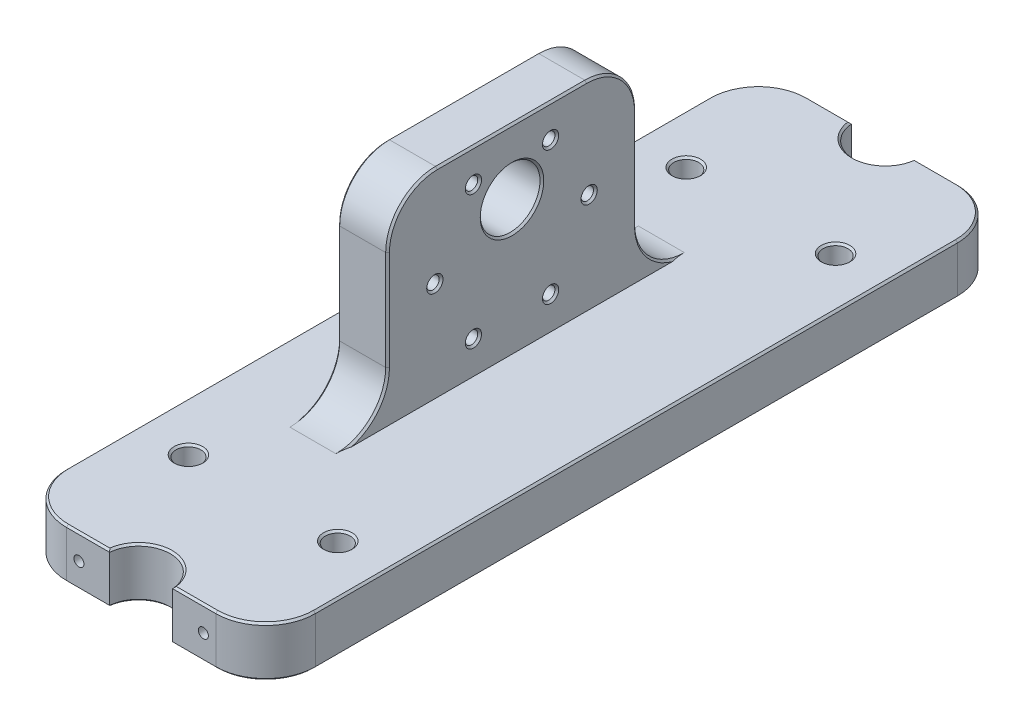
SolidWorks part; units mm, degrees
material "Nylon 101"
ref_plane "Front" through (0, 0, 0) normal (0, 0, 1) x (1, 0, 0)
ref_plane "Top" through (0, 0, 0) normal (0, 1, 0) x (1, 0, 0)
ref_plane "Right" through (0, 0, 0) normal (1, 0, 0) x (0, 0, -1)
sketch "Sketch1" plane through (0, 0, 0) normal (0, 1, 0) x (1, 0, 0)
  line L0 (-25, -75) -> (25, -75) construction
  line L1 (-15, 50) -> (15, 50) construction
  line L2 (0, -75) -> (0, 75) construction
  line L3 (-25, -75) -> (-25, 75)
  line L4 (25, -75) -> (25, 75)
  line L5 (25, 0) -> (0, 0) construction
  line L6 (25, 17) -> (97.2, 17)
  line L7 (25, 17) -> (25, -17)
  line L8 (25, -17) -> (97.2, -17)
  line L9 (97.2, 17) -> (97.2, -17)
  line L10 (-15, 50) -> (-15, -50) construction
  line L11 (-15, -50) -> (15, -50) construction
  line L12 (15, 50) -> (15, -50) construction
  line L13 (-25, -75.5) -> (25, -75.5)
  line L14 (-25, -74.5) -> (25, -74.5)
  line L15 (-25, 75.5) -> (25, 75.5)
  line L16 (-25, 74.5) -> (25, 74.5)
  circle A0 centre (0, 75) radius 6.35
  circle A1 centre (0, -75) radius 6.35
  arc A2 (-25, -75) -> (25, -75) centre (0, -75) ccw
  arc A3 (25, 75) -> (-25, 75) centre (0, 75) ccw
  circle A6 centre (-15, 50) radius 2.5
  circle A7 centre (-15, -50) radius 2.5
  circle A8 centre (15, -50) radius 2.5
  circle A9 centre (15, 50) radius 2.5
  point P8 (0, 0)
  point P24 (0, -50)
  dimension "D2" = 12.7
  dimension "D5" = 25
  dimension "D1" = 5
  dimension "D3" = 150
  dimension "D4" = 25
  dimension "D6" = 25
  dimension "D7" = 34
  dimension "D8" = 72.2
  dimension "D9" = 30
  dimension "D10" = 0.5
  dimension "D11" = 0.5
extrude "Boss-Extrude1" add sketch "Sketch1" along normal blind 10 contours A1 L14 L4 L16 A0 L3 A9 A8 A7 A6 region at (0, 0, 0)
sketch "Sketch2" plane through (0, 0, 0) normal (0, 1, 0) x (1, 0, 0)
  line L1 (0, 25) -> (-10, 25)
  line L2 (0, 25) -> (0, -25)
  line L3 (0, -25) -> (-10, -25)
  line L4 (-10, 25) -> (-10, -25)
  line L6 (25, 0) -> (0, 0) construction
  line L7 (25, 0) -> (0, 0) construction
  dimension "D1" = 50
  dimension "D2" = 10
extrude "Boss-Extrude2" add sketch "Sketch2" along normal blind 50
sketch "Sketch3" plane through (25, 0, 0) normal (1, 0, 0) x (0, 0, -1)
  line L0 (-25, 10) -> (25, 10) construction
  line L1 (0, 10) -> (0, 50) construction
  line L3 (-25, 50) -> (25, 50) construction
  circle A0 centre (0, 30) radius 15.5 construction
  circle A1 centre (0, 30) radius 18.4 construction
  circle A2 centre (-15.5, 30) radius 1.25
  circle A8 centre (0, 37) radius 3 construction
  circle A9 centre (0, 37) radius 6
  circle A10 centre (-7.75, 43.4234) radius 1.25
  circle A11 centre (7.75, 43.4234) radius 1.25
  circle A12 centre (15.5, 30) radius 1.25
  circle A13 centre (7.75, 16.5766) radius 1.25
  circle A14 centre (-7.75, 16.5766) radius 1.25
  dimension "D1" = 31
  dimension "D2" = 2.5
  dimension "D3" = 36.8
  dimension "D4" = 12
  dimension "D6" = 6
  dimension "D7" = 6
  dimension "D5" = 7
extrude "Cut-Extrude1" cut sketch "Sketch3" against normal through all
fillet "Fillet1" radius 10 8 edges at (-25, 5, -74.5) (25, 5, -74.5) (-25, 5, 74.5) (25, 5, 74.5) (-5, 10, -25) (-5, 50, -25) (-5, 50, 25) (-5, 10, 25)
sketch "Sketch4" plane through (0, 0, 74.5) normal (0, 0, 1) x (1, 0, 0)
  line L0 (-12.5, 0) -> (-12.5, 10) construction
  line L1 (-15, 0) -> (-6.3303, 0) construction
  line L2 (12.5, 10) -> (12.5, 0) construction
  line L3 (6.3303, 0) -> (15, 0) construction
  line L8 (-15, 10) -> (-6.3303, 10) construction
  line L9 (6.3303, 10) -> (15, 10) construction
  circle A0 centre (-12.5, 5) radius 1
  circle A1 centre (12.5, 5) radius 1
  dimension "D1" = 2
  dimension "D2" = 12.5
  dimension "D3" = 12.5
extrude "Cut-Extrude2" cut sketch "Sketch4" against normal blind 5
extrude "Cut-Extrude3" cut sketch "Sketch4<2>" along normal blind 5 from surface starting at face at (10.6651, 5, -74.5)
sketch "Sketch4<2>" plane through (0, 0, 74.5) normal (0, 0, 1) x (1, 0, 0) same geometry as "Sketch4"
chamfer "Chamfer1" distance 0.381 angle 45 60 edges at (0, 10, -68.65) (10.6651, 10, -74.5) (22.0711, 10, -71.5711) (25, 10, 0) (22.0711, 10, 71.5711) (10.6651, 10, 74.5) (0, 10, 68.65) (-10.6651, 10, 74.5) (-22.0711, 10, 71.5711) (-25, 10, 0) (-22.0711, 10, -71.5711) (-10.6651, 10, -74.5) (-15, 0, 52.5) (-15, 10, 52.5) (15, 0, 52.5) (15, 10, 52.5) (15, 0, -47.5) (15, 10, -47.5) (-15, 0, -47.5) (-15, 10, -47.5) (0, 30, -14.25) (-10, 30, -16.75) (0, 43.4234, -6.5) (-10, 43.4234, -9) (0, 43.4234, 9) (-10, 43.4234, 6.5) (0, 30, 16.75) (-10, 30, 14.25) (0, 16.5766, 9) (-10, 16.5766, 6.5) (0, 16.5766, -6.5) (-10, 16.5766, -9) (0, 37, 6) (-10, 37, -6) (0, 0, -68.65) (-10.6651, 0, -74.5) (10.6651, 0, -74.5) (-22.0711, 0, -71.5711) (22.0711, 0, -71.5711) (-25, 0, 0) (25, 0, 0) (-22.0711, 0, 71.5711) (22.0711, 0, 71.5711) (-10.6651, 0, 74.5) (0, 0, 68.65) (10.6651, 0, 74.5) (0, 12.9289, 27.9289) (0, 30, 25) (0, 47.0711, 22.0711) (0, 50, 0) (0, 47.0711, -22.0711) (0, 12.9289, -27.9289) (0, 30, -25) (-10, 12.9289, 27.9289) (-10, 30, 25) (-10, 47.0711, 22.0711) (-10, 50, 0) (-10, 47.0711, -22.0711) (-10, 30, -25) (-10, 12.9289, -27.9289)
